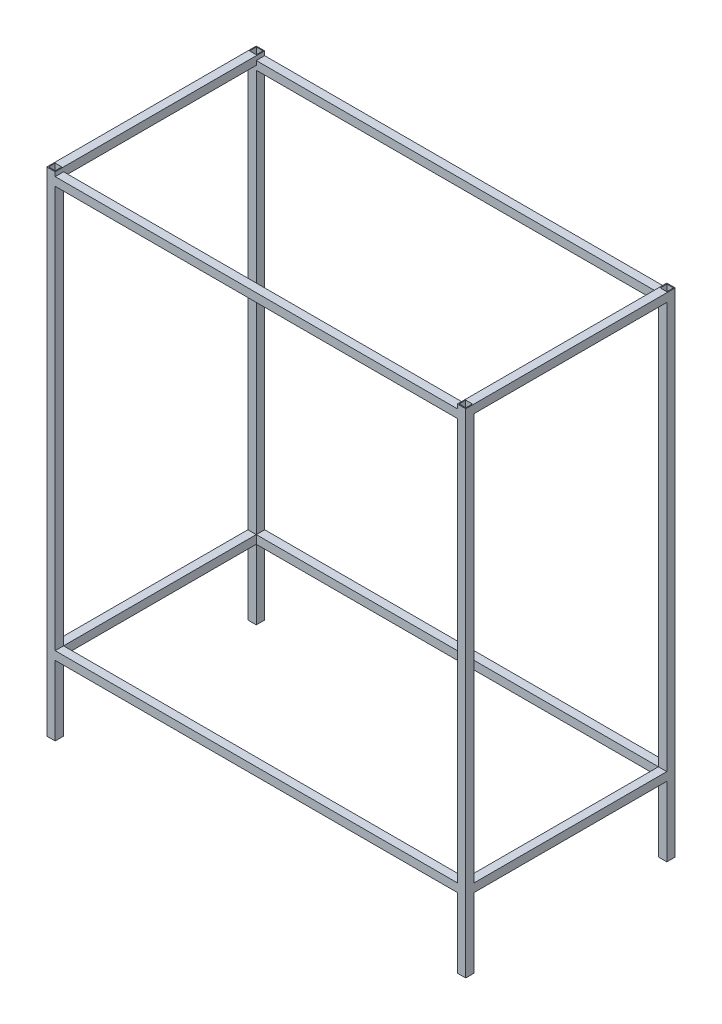
SolidWorks part; units mm, degrees
material "AISI 1035 Сталь (SS)"
ref_plane "Спереди" through (0, 0, 0) normal (0, 0, 1) x (1, 0, 0)
ref_plane "Сверху" through (0, 0, 0) normal (0, 1, 0) x (1, 0, 0)
ref_plane "Справа" through (0, 0, 0) normal (1, 0, 0) x (0, 0, -1)
sketch "Эскиз1" plane through (0, 0, 0) normal (0, 0, 1) x (1, 0, 0)
  line L0 (30, 1765) -> (30, 1750)
  line L1 (0, 0) -> (30, 0)
  line L2 (0, 0) -> (0, 1765)
  line L3 (0, 1765) -> (30, 1765)
  line L4 (1500, 0) -> (1500, 1765)
  line L5 (30, 1750) -> (1470, 1750)
  line L6 (1470, 1750) -> (1470, 1765)
  line L7 (1470, 0) -> (1470, 250)
  line L8 (1470, 250) -> (30, 250)
  line L9 (30, 250) -> (30, 0)
  line L10 (1470, 0) -> (1500, 0)
  line L11 (1470, 1765) -> (1500, 1765)
  line L13 (30, 1720) -> (1470, 1720)
  line L14 (30, 1720) -> (30, 280)
  line L15 (30, 280) -> (1470, 280)
  line L16 (1470, 1720) -> (1470, 280)
  dimension "D1" = 1500
  dimension "D2" = 1500
  dimension "D3" = 30
  dimension "D4" = 30
  dimension "D5" = 15
  dimension "D6" = 250
  dimension "D7" = 30
  dimension "D8" = 30
  dimension "D9" = 30
extrude "Бобышка-Вытянуть1" add sketch "Эскиз1" along normal blind 750
sketch "Эскиз2" plane through (1500, 0, 0) normal (1, 0, 0) x (0, 0, -1)
  line L0 (0, 1720) -> (0, 280) construction
  line L1 (-720, 1735) -> (-30, 1735)
  line L2 (-720, 1735) -> (-720, 280)
  line L3 (-720, 280) -> (-30, 280)
  line L4 (-30, 1735) -> (-30, 280)
  line L5 (-750, 0) -> (-750, 1765) construction
  line L6 (-750, 1765) -> (0, 1765) construction
  line L7 (-750, 0) -> (0, 0) construction
  dimension "D1" = 30
  dimension "D2" = 30
  dimension "D3" = 30
  dimension "D4" = 280
extrude "Вырез-Вытянуть1" cut sketch "Эскиз2" against normal through all
sketch "Эскиз3" plane through (0, 1750, 0) normal (0, 1, 0) x (1, 0, 0)
  line L0 (1470, -750) -> (1470, 0) construction
  line L1 (1470, -720) -> (30, -720)
  line L2 (1470, -720) -> (1470, -30)
  line L3 (1470, -30) -> (30, -30)
  line L4 (30, -720) -> (30, -30)
  line L5 (30, -750) -> (30, 0) construction
  line L6 (1470, -750) -> (30, -750) construction
  line L7 (30, 0) -> (1470, 0) construction
  dimension "D1" = 30
  dimension "D2" = 30
extrude "Вырез-Вытянуть2" cut sketch "Эскиз3" against normal through all
sketch "Эскиз4" plane through (0, 1765, 0) normal (0, 1, 0) x (1, 0, 0)
  line L0 (0, 0) -> (30, 0) construction
  line L1 (3, -3) -> (27, -3)
  line L2 (3, -3) -> (3, -27)
  line L3 (3, -27) -> (27, -27)
  line L4 (27, -3) -> (27, -27)
  line L5 (0, -750) -> (0, 0) construction
  line L6 (1470, -30) -> (30, -30) construction
  line L7 (1500, -750) -> (1500, 0) construction
  line L8 (1473, -723) -> (1497, -723)
  line L9 (1473, -723) -> (1473, -747)
  line L10 (1473, -747) -> (1497, -747)
  line L11 (1497, -723) -> (1497, -747)
  line L12 (1500, -750) -> (1470, -750) construction
  line L13 (30, -720) -> (1470, -720) construction
  line L14 (1470, -750) -> (1470, -720) construction
  line L16 (1473, -3) -> (1497, -3)
  line L17 (1473, -3) -> (1473, -27)
  line L18 (1473, -27) -> (1497, -27)
  line L19 (1497, -3) -> (1497, -27)
  line L20 (3, -723) -> (27, -723)
  line L21 (3, -723) -> (3, -747)
  line L22 (3, -747) -> (27, -747)
  line L23 (27, -723) -> (27, -747)
  dimension "D1" = 3
  dimension "D2" = 3
  dimension "D3" = 3
  dimension "D4" = 3
  dimension "D5" = 3
  dimension "D6" = 3
  dimension "D7" = 3
extrude "Вырез-Вытянуть3" cut sketch "Эскиз4" against normal through all
sketch "Эскиз5" plane through (1500, 0, 0) normal (1, 0, 0) x (0, 0, -1)
  line L0 (-720, 1735) -> (-720, 280) construction
  line L1 (-720, 250) -> (-30, 250)
  line L2 (-720, 250) -> (-720, 0)
  line L3 (-720, 0) -> (-30, 0)
  line L4 (-30, 250) -> (-30, 0)
  line L5 (-30, 280) -> (-30, 1735) construction
  line L6 (-720, 280) -> (-30, 280) construction
  line L7 (-750, 0) -> (0, 0) construction
  dimension "D1" = 30
extrude "Вырез-Вытянуть4" cut sketch "Эскиз5" against normal through all
